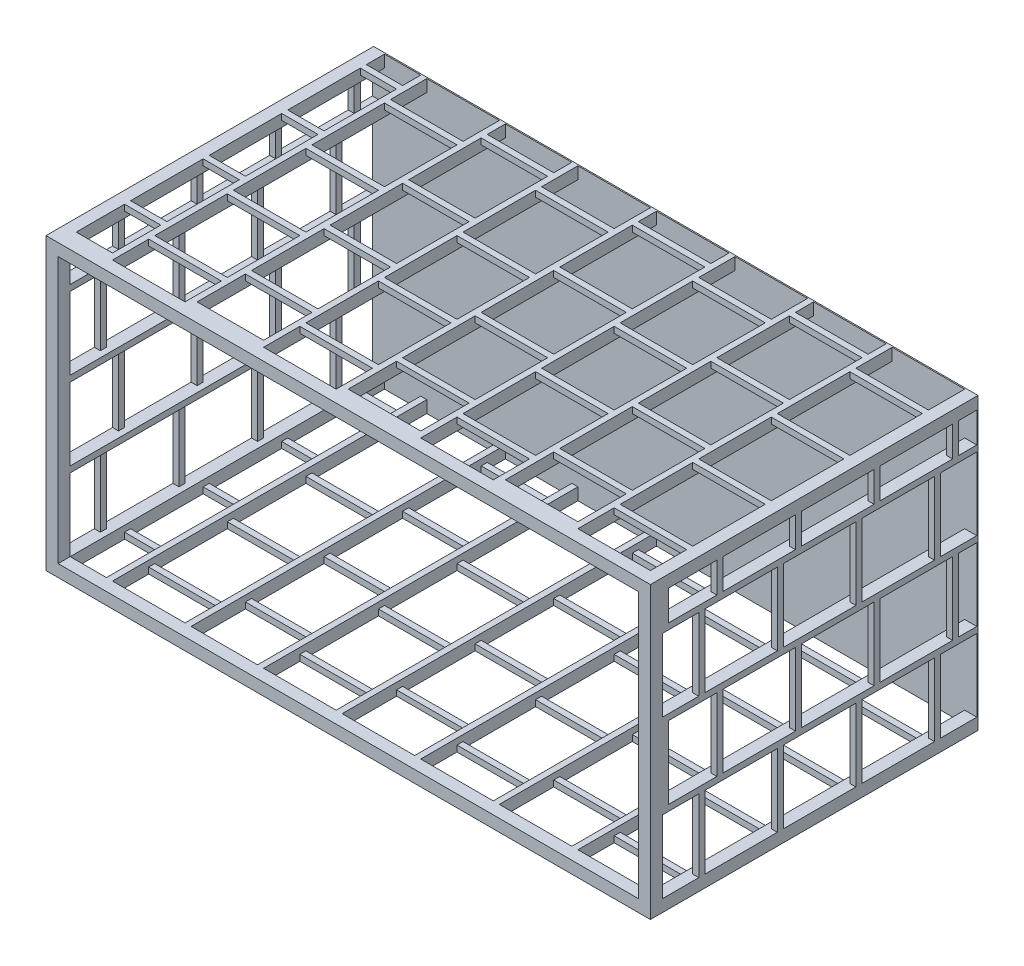
SolidWorks part; units mm, degrees
ref_plane "Plan de face" through (0, 0, 0) normal (0, 0, 1) x (1, 0, 0)
ref_plane "Plan de dessus" through (0, 0, 0) normal (0, 1, 0) x (1, 0, 0)
ref_plane "Plan de droite" through (0, 0, 0) normal (1, 0, 0) x (0, 0, -1)
sketch "Esquisse1" plane through (0, 0, 0) normal (0, 0, 1) x (1, 0, 0)
  line L1 (2500, -1200) -> (-2500, -1200)
  line L2 (2500, -1200) -> (2500, 1200)
  line L3 (2500, 1200) -> (-2500, 1200)
  line L4 (-2500, -1200) -> (-2500, 1200)
  line L5 (2500, -1200) -> (-2500, 1200) construction
  line L6 (2500, 1200) -> (-2500, -1200) construction
  point P0 (0, 0)
extrude "Boss.-Extru.1" add sketch "Esquisse1" along normal blind 10
sketch "Esquisse2" plane through (0, 0, 10) normal (0, 0, 1) x (1, 0, 0)
  line L0 (-2400, -1200) -> (-2400, -1100) construction
  line L1 (-2500, -1200) -> (2500, -1200) construction
  line L2 (-2400, -1100) -> (-2500, -1100) construction
  line L3 (-2500, 1200) -> (-2500, -1200) construction
  line L4 (0, 1200) -> (0, -1200) construction
  line L5 (-2500, -1200) -> (-2400, -1200)
  line L6 (-2500, -1200) -> (-2500, -1100)
  line L7 (-2500, -1100) -> (-2400, -1100)
  line L8 (-2400, -1200) -> (-2400, -1100)
  line L9 (2500, 1200) -> (-2500, 1200) construction
  line L10 (-2500, 0) -> (2500, 0) construction
  line L11 (2500, -1200) -> (2500, 1200) construction
  line L12 (2400, -1100) -> (2500, -1100) construction
  line L13 (2400, -1200) -> (2400, -1100) construction
  line L14 (2400, -1200) -> (2400, -1100)
  line L15 (2500, -1100) -> (2400, -1100)
  line L16 (2500, -1200) -> (2500, -1100)
  line L17 (2500, -1200) -> (2400, -1200)
  line L18 (2400, 1200) -> (2400, 1100) construction
  line L19 (2400, 1100) -> (2500, 1100) construction
  line L20 (2500, 1200) -> (2400, 1200)
  line L21 (2500, 1200) -> (2500, 1100)
  line L22 (2500, 1100) -> (2400, 1100)
  line L23 (2400, 1200) -> (2400, 1100)
  line L24 (-2400, 1100) -> (-2500, 1100) construction
  line L25 (-2400, 1200) -> (-2400, 1100) construction
  line L26 (-2400, 1200) -> (-2400, 1100)
  line L27 (-2500, 1100) -> (-2400, 1100)
  line L28 (-2500, 1200) -> (-2500, 1100)
  line L29 (-2500, 1200) -> (-2400, 1200)
extrude "Boss.-Extru.3" add sketch "Esquisse2" along normal blind 2700
sketch "Esquisse3" plane through (2400, 0, 0) normal (-1, 0, 0) x (0, 0, 1)
  line L0 (2710, 1100) -> (2610, 1100) construction
  line L1 (2710, 1100) -> (10, 1100) construction
  line L2 (2610, 1100) -> (2610, 1200) construction
  line L3 (2710, 1200) -> (10, 1200) construction
  line L4 (2610, 1200) -> (2710, 1200) construction
  line L5 (2710, 1200) -> (2710, 1100) construction
  line L7 (2710, 1100) -> (2610, 1100)
  line L8 (2710, 1100) -> (2710, 1200)
  line L9 (2710, 1200) -> (2610, 1200)
  line L10 (2610, 1100) -> (2610, 1200)
extrude "Boss.-Extru.4" add sketch "Esquisse3" along normal up to next
sketch "Esquisse4" plane through (0, 1100, 0) normal (0, -1, 0) x (1, 0, 0)
  line L1 (-2500, 2710) -> (-2400, 2710)
  line L2 (-2500, 2710) -> (-2500, 2610)
  line L3 (-2500, 2610) -> (-2400, 2610)
  line L4 (-2400, 2710) -> (-2400, 2610)
  line L5 (2400, 2610) -> (2500, 2610)
  line L6 (2400, 2610) -> (2400, 2710)
  line L7 (2400, 2710) -> (2500, 2710)
  line L8 (2500, 2610) -> (2500, 2710)
extrude "Boss.-Extru.6" add sketch "Esquisse4" along normal up to next
sketch "Esquisse5" plane through (-2400, 0, 0) normal (1, 0, 0) x (0, 0, -1)
  line L1 (-2710, -1200) -> (-2610, -1200)
  line L2 (-2710, -1200) -> (-2710, -1100)
  line L3 (-2710, -1100) -> (-2610, -1100)
  line L4 (-2610, -1200) -> (-2610, -1100)
extrude "Boss.-Extru.7" add sketch "Esquisse5" along normal up to next
sketch "Esquisse6" plane through (0, 0, 10) normal (0, 0, 1) x (1, 0, 0)
  line L0 (2400, 1200) -> (1800, 1200) construction
  line L1 (2400, 1200) -> (-2400, 1200) construction
  line L2 (2500, 0) -> (-2500, 0) construction
  line L3 (1800, 1200) -> (1750, 1200)
  line L4 (1800, 1200) -> (1800, 1100)
  line L5 (1800, 1100) -> (1750, 1100)
  line L6 (1750, 1200) -> (1750, 1100)
  line L7 (1100, 1200) -> (1150, 1200)
  line L8 (1100, 1200) -> (1100, 1100)
  line L9 (1100, 1100) -> (1150, 1100)
  line L10 (1150, 1200) -> (1150, 1100)
  line L11 (450, 1200) -> (500, 1200)
  line L12 (450, 1200) -> (450, 1100)
  line L13 (450, 1100) -> (500, 1100)
  line L14 (500, 1200) -> (500, 1100)
  line L15 (-200, 1100) -> (-150, 1100)
  line L16 (-200, 1100) -> (-200, 1200)
  line L17 (-200, 1200) -> (-150, 1200)
  line L18 (-150, 1100) -> (-150, 1200)
  line L19 (-850, 1100) -> (-800, 1100)
  line L20 (-850, 1100) -> (-850, 1200)
  line L21 (-850, 1200) -> (-800, 1200)
  line L22 (-800, 1100) -> (-800, 1200)
  line L23 (-1450, 1100) -> (-1400, 1100)
  line L24 (-1450, 1100) -> (-1450, 1200)
  line L25 (-1450, 1200) -> (-1400, 1200)
  line L26 (-1400, 1100) -> (-1400, 1200)
  line L27 (-2100, 1100) -> (-2050, 1100)
  line L28 (-2100, 1100) -> (-2100, 1200)
  line L29 (-2100, 1200) -> (-2050, 1200)
  line L30 (-2050, 1100) -> (-2050, 1200)
  line L31 (2500, -1100) -> (2500, 1100) construction
  line L32 (-2500, 1100) -> (-2500, -1100) construction
  line L33 (2400, -1200) -> (1800, -1200) construction
  line L34 (-2050, -1100) -> (-2050, -1200)
  line L35 (-2100, -1200) -> (-2050, -1200)
  line L36 (-2100, -1100) -> (-2100, -1200)
  line L37 (-2100, -1100) -> (-2050, -1100)
  line L38 (-1400, -1100) -> (-1400, -1200)
  line L39 (-1450, -1200) -> (-1400, -1200)
  line L40 (-1450, -1100) -> (-1450, -1200)
  line L41 (-1450, -1100) -> (-1400, -1100)
  line L42 (-800, -1100) -> (-800, -1200)
  line L43 (-850, -1200) -> (-800, -1200)
  line L44 (-850, -1100) -> (-850, -1200)
  line L45 (-850, -1100) -> (-800, -1100)
  line L46 (-150, -1100) -> (-150, -1200)
  line L47 (-200, -1200) -> (-150, -1200)
  line L48 (-200, -1100) -> (-200, -1200)
  line L49 (-200, -1100) -> (-150, -1100)
  line L50 (500, -1200) -> (500, -1100)
  line L51 (450, -1100) -> (500, -1100)
  line L52 (450, -1200) -> (450, -1100)
  line L53 (450, -1200) -> (500, -1200)
  line L54 (1150, -1200) -> (1150, -1100)
  line L55 (1100, -1100) -> (1150, -1100)
  line L56 (1100, -1200) -> (1100, -1100)
  line L57 (1100, -1200) -> (1150, -1200)
  line L58 (1750, -1200) -> (1750, -1100)
  line L59 (1800, -1100) -> (1750, -1100)
  line L60 (1800, -1200) -> (1800, -1100)
  line L61 (1800, -1200) -> (1750, -1200)
  point P16 (450, 1150)
  dimension "D1" = 600
  dimension "D2" = 50
  dimension "D3" = 600
  dimension "D4" = 50
  dimension "D5" = 100
  dimension "D6" = 600
  dimension "D7" = 50
  dimension "D8" = 100
  dimension "D9" = 600
  dimension "D10" = 50
  dimension "D11" = 100
  dimension "D12" = 600
  dimension "D13" = 50
  dimension "D14" = 100
  dimension "D15" = 600
  dimension "D16" = 50
  dimension "D17" = 100
  dimension "D18" = 600
  dimension "D19" = 50
  dimension "D20" = 100
  dimension "D21" = 100
extrude "Boss.-Extru.8" add sketch "Esquisse6" along normal up to next
sketch "Esquisse7" plane through (0, 0, 10) normal (0, 0, 1) x (1, 0, 0)
  line L0 (2500, -1100) -> (2500, 1100) construction
  line L1 (2500, -500) -> (2400, -500)
  line L2 (2500, -500) -> (2500, -450)
  line L3 (2500, -450) -> (2400, -450)
  line L4 (2400, -500) -> (2400, -450)
  line L5 (0, -1200) -> (0, 1200) construction
  line L6 (2500, 150) -> (2400, 150)
  line L7 (2500, 150) -> (2500, 200)
  line L8 (2500, 200) -> (2400, 200)
  line L9 (2400, 150) -> (2400, 200)
  line L10 (2500, 800) -> (2400, 800)
  line L11 (2500, 800) -> (2500, 850)
  line L12 (2500, 850) -> (2400, 850)
  line L13 (2400, 800) -> (2400, 850)
  line L14 (-150, -1200) -> (450, -1200) construction
  line L15 (450, 1200) -> (-150, 1200) construction
  line L16 (-2500, 850) -> (-2400, 850)
  line L17 (-2500, 800) -> (-2500, 850)
  line L18 (-2500, 800) -> (-2400, 800)
  line L19 (-2400, -500) -> (-2400, -450)
  line L20 (-2500, -450) -> (-2400, -450)
  line L21 (-2500, -500) -> (-2500, -450)
  line L22 (-2500, -500) -> (-2400, -500)
  line L23 (-2400, 800) -> (-2400, 850)
  line L24 (-2400, 150) -> (-2400, 200)
  line L25 (-2500, 200) -> (-2400, 200)
  line L26 (-2500, 150) -> (-2500, 200)
  line L27 (-2500, 150) -> (-2400, 150)
  dimension "D1" = 600
  dimension "D2" = 100
  dimension "D3" = 50
  dimension "D4" = 600
  dimension "D5" = 100
  dimension "D6" = 50
  dimension "D7" = 600
  dimension "D8" = 100
  dimension "D9" = 50
extrude "Boss.-Extru.9" add sketch "Esquisse7" along normal up to next
sketch "Esquisse8" plane through (2400, 0, 0) normal (-1, 0, 0) x (0, 0, 1)
  line L0 (2610, 1200) -> (10, 1200) construction
  line L1 (310, 1200) -> (360, 1200)
  line L2 (310, 1200) -> (310, 1150)
  line L3 (310, 1150) -> (360, 1150)
  line L4 (360, 1200) -> (360, 1150)
  line L5 (0, 0) -> (2710, 0) construction
  line L6 (960, 1200) -> (1010, 1200)
  line L7 (960, 1200) -> (960, 1150)
  line L8 (960, 1150) -> (1010, 1150)
  line L9 (1010, 1200) -> (1010, 1150)
  line L10 (1610, 1200) -> (1660, 1200)
  line L11 (1610, 1200) -> (1610, 1150)
  line L12 (1610, 1150) -> (1660, 1150)
  line L13 (1660, 1200) -> (1660, 1150)
  line L14 (2260, 1200) -> (2310, 1200)
  line L15 (2260, 1200) -> (2260, 1150)
  line L16 (2260, 1150) -> (2310, 1150)
  line L17 (2310, 1200) -> (2310, 1150)
  line L18 (2710, 1200) -> (2710, -1200) construction
  line L19 (2310, -1200) -> (2310, -1150)
  line L20 (2260, -1150) -> (2310, -1150)
  line L21 (2260, -1200) -> (2260, -1150)
  line L22 (2260, -1200) -> (2310, -1200)
  line L23 (1660, -1200) -> (1660, -1150)
  line L24 (1610, -1150) -> (1660, -1150)
  line L25 (1610, -1200) -> (1610, -1150)
  line L26 (1610, -1200) -> (1660, -1200)
  line L27 (1010, -1200) -> (1010, -1150)
  line L28 (960, -1150) -> (1010, -1150)
  line L29 (960, -1200) -> (960, -1150)
  line L30 (960, -1200) -> (1010, -1200)
  line L31 (360, -1200) -> (360, -1150)
  line L32 (310, -1150) -> (360, -1150)
  line L33 (310, -1200) -> (310, -1150)
  line L34 (310, -1200) -> (360, -1200)
  dimension "D1" = 300
  dimension "D2" = 50
  dimension "D3" = 50
  dimension "D4" = 600
  dimension "D5" = 50
  dimension "D6" = 50
  dimension "D7" = 600
  dimension "D8" = 50
  dimension "D9" = 50
  dimension "D10" = 600
  dimension "D12" = 50
extrude "Boss.-Extru.11" add sketch "Esquisse8" along normal up to next
sketch "Esquisse9" plane through (1750, 0, 0) normal (-1, 0, 0) x (0, 0, 1)
  line L0 (2610, 1200) -> (10, 1200) construction
  line L1 (10, 1200) -> (10, 1100) construction
  line L2 (160, 1200) -> (210, 1200)
  line L3 (160, 1200) -> (160, 1150)
  line L4 (160, 1150) -> (210, 1150)
  line L6 (210, 1200) -> (210, 1150)
  line L7 (860, 1200) -> (810, 1200)
  line L8 (860, 1200) -> (860, 1150)
  line L9 (860, 1150) -> (810, 1150)
  line L10 (0, 0) -> (2710, 0) construction
  line L11 (810, 1200) -> (810, 1150)
  line L12 (1510, 1200) -> (1460, 1200)
  line L13 (1510, 1200) -> (1510, 1150)
  line L14 (1510, 1150) -> (1460, 1150)
  line L15 (1460, 1200) -> (1460, 1150)
  line L16 (2110, 1200) -> (2160, 1200)
  line L17 (2110, 1200) -> (2110, 1150)
  line L18 (2110, 1150) -> (2160, 1150)
  line L19 (2160, 1200) -> (2160, 1150)
  line L20 (2610, 1200) -> (2560, 1200)
  line L21 (2610, 1200) -> (2610, 1150)
  line L22 (2610, 1150) -> (2560, 1150)
  line L23 (2710, 1200) -> (2710, -1200) construction
  line L24 (2560, -1200) -> (2560, -1150)
  line L25 (2610, -1150) -> (2560, -1150)
  line L26 (2610, -1200) -> (2610, -1150)
  line L27 (2610, -1200) -> (2560, -1200)
  line L28 (2160, -1200) -> (2160, -1150)
  line L29 (2110, -1150) -> (2160, -1150)
  line L30 (2110, -1200) -> (2110, -1150)
  line L31 (2110, -1200) -> (2160, -1200)
  line L32 (1460, -1200) -> (1460, -1150)
  line L33 (1510, -1150) -> (1460, -1150)
  line L34 (1510, -1200) -> (1510, -1150)
  line L35 (1510, -1200) -> (1460, -1200)
  line L36 (810, -1200) -> (810, -1150)
  line L37 (860, -1150) -> (810, -1150)
  line L38 (860, -1200) -> (860, -1150)
  line L39 (860, -1200) -> (810, -1200)
  line L40 (210, -1200) -> (210, -1150)
  line L41 (160, -1150) -> (210, -1150)
  line L42 (160, -1200) -> (160, -1150)
  line L43 (160, -1200) -> (210, -1200)
  line L44 (2560, 1200) -> (2560, 1150)
  dimension "D2" = 150
  dimension "D3" = 50
  dimension "D4" = 50
  dimension "D5" = 50
  dimension "D6" = 50
  dimension "D7" = 50
  dimension "D8" = 50
  dimension "D9" = 50
  dimension "D10" = 50
  dimension "D11" = 50
  dimension "D12" = 400
  dimension "D13" = 600
  dimension "D14" = 600
  dimension "D15" = 50
  dimension "D16" = 600
extrude "Boss.-Extru.12" add sketch "Esquisse9" along normal up to next
sketch "Esquisse10" plane through (1100, 0, 0) normal (-1, 0, 0) x (0, 0, 1)
  line L0 (2610, 1200) -> (10, 1200) construction
  line L1 (2260, -1200) -> (2260, -1150)
  line L2 (310, 1200) -> (360, 1200)
  line L3 (310, 1200) -> (310, 1150)
  line L4 (310, 1150) -> (360, 1150)
  line L7 (0, 0) -> (2710, 0) construction
  line L8 (360, 1200) -> (360, 1150)
  line L9 (960, 1200) -> (1010, 1200)
  line L10 (960, 1200) -> (960, 1150)
  line L11 (960, 1150) -> (1010, 1150)
  line L12 (1010, 1200) -> (1010, 1150)
  line L13 (1660, 1200) -> (1610, 1200)
  line L14 (1660, 1200) -> (1660, 1150)
  line L15 (1660, 1150) -> (1610, 1150)
  line L16 (1610, 1200) -> (1610, 1150)
  line L17 (2310, 1200) -> (2260, 1200)
  line L18 (2310, 1200) -> (2310, 1150)
  line L19 (2310, 1150) -> (2260, 1150)
  line L20 (2710, 1200) -> (2710, -1200) construction
  line L21 (2310, -1150) -> (2260, -1150)
  line L22 (2310, -1200) -> (2310, -1150)
  line L23 (2310, -1200) -> (2260, -1200)
  line L24 (1610, -1200) -> (1610, -1150)
  line L25 (1660, -1150) -> (1610, -1150)
  line L26 (1660, -1200) -> (1660, -1150)
  line L27 (1660, -1200) -> (1610, -1200)
  line L28 (1010, -1200) -> (1010, -1150)
  line L29 (960, -1150) -> (1010, -1150)
  line L30 (960, -1200) -> (960, -1150)
  line L31 (960, -1200) -> (1010, -1200)
  line L32 (360, -1200) -> (360, -1150)
  line L33 (310, -1150) -> (360, -1150)
  line L34 (310, -1200) -> (310, -1150)
  line L35 (310, -1200) -> (360, -1200)
  line L37 (2260, 1200) -> (2260, 1150)
  point P43 (1610, 1175)
  dimension "D2" = 50
  dimension "D3" = 50
  dimension "D4" = 50
  dimension "D5" = 50
  dimension "D6" = 50
  dimension "D7" = 50
  dimension "D8" = 50
  dimension "D9" = 600
  dimension "D10" = 600
  dimension "D11" = 50
  dimension "D12" = 600
extrude "Boss.-Extru.13" add sketch "Esquisse10" along normal up to next
sketch "Esquisse11" plane through (450, 0, 0) normal (-1, 0, 0) x (0, 0, 1)
  line L0 (2610, 1200) -> (10, 1200) construction
  line L1 (2610, 1200) -> (2610, 1100) construction
  line L2 (2560, 1200) -> (2610, 1200)
  line L3 (2560, 1200) -> (2560, 1150)
  line L4 (2560, 1150) -> (2610, 1150)
  line L6 (2110, -1200) -> (2110, -1154.4562)
  line L7 (0, 0) -> (2710, 0) construction
  line L8 (2610, -1200) -> (2610, -1150)
  line L9 (2160, 1200) -> (2110, 1200)
  line L10 (2160, 1200) -> (2160, 1154.4562)
  line L11 (2160, 1154.4562) -> (2110, 1154.4562)
  line L12 (1510, 1200) -> (1460, 1200)
  line L13 (1510, 1200) -> (1510, 1150)
  line L14 (1510, 1150) -> (1460, 1150)
  line L15 (1460, 1200) -> (1460, 1150)
  line L16 (160, 1200) -> (210, 1200)
  line L17 (160, 1200) -> (160, 1150)
  line L18 (160, 1150) -> (210, 1150)
  line L19 (210, 1200) -> (210, 1150)
  line L20 (860, 1200) -> (810, 1200)
  line L21 (860, 1200) -> (860, 1150)
  line L22 (860, 1150) -> (810, 1150)
  line L23 (810, 1200) -> (810, 1150)
  line L24 (2710, 1200) -> (2710, -1200) construction
  line L25 (810, -1200) -> (810, -1150)
  line L26 (860, -1150) -> (810, -1150)
  line L27 (860, -1200) -> (860, -1150)
  line L28 (860, -1200) -> (810, -1200)
  line L29 (210, -1200) -> (210, -1150)
  line L30 (160, -1150) -> (210, -1150)
  line L31 (160, -1200) -> (160, -1150)
  line L32 (160, -1200) -> (210, -1200)
  line L33 (1460, -1200) -> (1460, -1150)
  line L34 (1510, -1150) -> (1460, -1150)
  line L35 (1510, -1200) -> (1510, -1150)
  line L36 (1510, -1200) -> (1460, -1200)
  line L37 (2160, -1154.4562) -> (2110, -1154.4562)
  line L38 (2160, -1200) -> (2160, -1154.4562)
  line L39 (2160, -1200) -> (2110, -1200)
  line L40 (2560, -1150) -> (2610, -1150)
  line L41 (2560, -1200) -> (2560, -1150)
  line L42 (2560, -1200) -> (2610, -1200)
  line L45 (2610, 1200) -> (2610, 1150)
  line L46 (2110, 1200) -> (2110, 1154.4562)
  dimension "D2" = 50
  dimension "D3" = 50
  dimension "D4" = 400
  dimension "D5" = 50
  dimension "D6" = 50
  dimension "D7" = 50
  dimension "D8" = 50
  dimension "D9" = 50
  dimension "D10" = 50
  dimension "D11" = 600
  dimension "D12" = 600
  dimension "D13" = 600
extrude "Boss.-Extru.14" add sketch "Esquisse11" along normal up to next
sketch "Esquisse12" plane through (-200, 0, 0) normal (-1, 0, 0) x (0, 0, 1)
  line L0 (2610, 1200) -> (10, 1200) construction
  line L1 (10, 1200) -> (10, 1100) construction
  line L2 (360, 1200) -> (310, 1200)
  line L3 (360, 1200) -> (360, 1150)
  line L4 (360, 1150) -> (310, 1150)
  line L7 (2610, 1200) -> (2610, 1100) construction
  line L8 (0, 0) -> (2710, 0) construction
  line L10 (960, 1200) -> (1010, 1200)
  line L11 (960, 1200) -> (960, 1150)
  line L12 (960, 1150) -> (1010, 1150)
  line L13 (1010, 1200) -> (1010, 1150)
  line L14 (1610, 1200) -> (1660, 1200)
  line L15 (1610, 1200) -> (1610, 1150)
  line L16 (1610, 1150) -> (1660, 1150)
  line L17 (310, 1200) -> (310, 1150)
  line L18 (2310, 1200) -> (2260, 1200)
  line L19 (2310, 1200) -> (2310, 1150)
  line L20 (2310, 1150) -> (2260, 1150)
  line L21 (2710, 1200) -> (2710, -1200) construction
  line L22 (1660, -1200) -> (1660, -1150)
  line L23 (2260, -1200) -> (2260, -1150)
  line L24 (2310, -1150) -> (2260, -1150)
  line L25 (2310, -1200) -> (2310, -1150)
  line L26 (2310, -1200) -> (2260, -1200)
  line L27 (310, -1200) -> (310, -1150)
  line L28 (1610, -1150) -> (1660, -1150)
  line L29 (1610, -1200) -> (1610, -1150)
  line L30 (1610, -1200) -> (1660, -1200)
  line L31 (1010, -1200) -> (1010, -1150)
  line L32 (960, -1150) -> (1010, -1150)
  line L33 (960, -1200) -> (960, -1150)
  line L34 (960, -1200) -> (1010, -1200)
  line L35 (360, -1150) -> (310, -1150)
  line L36 (360, -1200) -> (360, -1150)
  line L37 (360, -1200) -> (310, -1200)
  line L38 (2260, 1200) -> (2260, 1150)
  line L39 (1660, 1200) -> (1660, 1150)
  dimension "D2" = 50
  dimension "D3" = 50
  dimension "D4" = 50
  dimension "D5" = 50
  dimension "D6" = 50
  dimension "D7" = 50
  dimension "D8" = 50
  dimension "D9" = 600
  dimension "D10" = 600
  dimension "D11" = 300
  dimension "D12" = 50
  dimension "D13" = 600
  dimension "D14" = 300
extrude "Boss.-Extru.15" add sketch "Esquisse12" along normal up to next
sketch "Esquisse13" plane through (-850, 0, 0) normal (-1, 0, 0) x (0, 0, 1)
  line L0 (2610, 1200) -> (10, 1200) construction
  line L1 (10, 1200) -> (10, 1100) construction
  line L2 (160, 1200) -> (210, 1200)
  line L3 (160, 1200) -> (160, 1150)
  line L4 (160, 1150) -> (210, 1150)
  line L7 (0, 0) -> (2710, 0) construction
  line L9 (810, 1200) -> (860, 1200)
  line L10 (810, 1200) -> (810, 1150)
  line L11 (810, 1150) -> (860, 1150)
  line L12 (860, 1200) -> (860, 1150)
  line L13 (1460, 1200) -> (1510, 1200)
  line L14 (1460, 1200) -> (1460, 1150)
  line L15 (1460, 1150) -> (1510, 1150)
  line L16 (1510, 1200) -> (1510, 1150)
  line L17 (2160, 1200) -> (2110, 1200)
  line L18 (2160, 1200) -> (2160, 1150)
  line L19 (2160, 1150) -> (2110, 1150)
  line L20 (2110, 1200) -> (2110, 1150)
  line L21 (2610, 1200) -> (2560, 1200)
  line L22 (2610, 1200) -> (2610, 1150)
  line L23 (2610, 1150) -> (2560, 1150)
  line L24 (2710, 1200) -> (2710, -1200) construction
  line L25 (210, -1200) -> (210, -1150)
  line L26 (2560, -1200) -> (2560, -1150)
  line L27 (2610, -1150) -> (2560, -1150)
  line L28 (2610, -1200) -> (2610, -1150)
  line L29 (2610, -1200) -> (2560, -1200)
  line L30 (2110, -1200) -> (2110, -1150)
  line L31 (2160, -1150) -> (2110, -1150)
  line L32 (2160, -1200) -> (2160, -1150)
  line L33 (2160, -1200) -> (2110, -1200)
  line L34 (1510, -1200) -> (1510, -1150)
  line L35 (1460, -1150) -> (1510, -1150)
  line L36 (1460, -1200) -> (1460, -1150)
  line L37 (1460, -1200) -> (1510, -1200)
  line L38 (860, -1200) -> (860, -1150)
  line L39 (810, -1150) -> (860, -1150)
  line L40 (810, -1200) -> (810, -1150)
  line L41 (810, -1200) -> (860, -1200)
  line L42 (160, -1150) -> (210, -1150)
  line L43 (160, -1200) -> (160, -1150)
  line L44 (160, -1200) -> (210, -1200)
  line L45 (2560, 1200) -> (2560, 1150)
  line L46 (210, 1200) -> (210, 1150)
  dimension "D2" = 50
  dimension "D3" = 50
  dimension "D4" = 50
  dimension "D5" = 50
  dimension "D6" = 50
  dimension "D7" = 50
  dimension "D8" = 50
  dimension "D9" = 50
  dimension "D10" = 50
  dimension "D11" = 400
  dimension "D12" = 600
  dimension "D13" = 600
  dimension "D14" = 50
  dimension "D15" = 600
  dimension "D16" = 150
extrude "Boss.-Extru.16" add sketch "Esquisse13" along normal up to next
sketch "Esquisse14" plane through (-1450, 0, 0) normal (-1, 0, 0) x (0, 0, 1)
  line L1 (10, 1200) -> (10, 1100) construction
  line L2 (360, 1200) -> (310, 1200)
  line L3 (360, 1200) -> (360, 1150)
  line L4 (360, 1150) -> (310, 1150)
  line L5 (2610, 1200) -> (10, 1200) construction
  line L7 (0, 0) -> (2710, 0) construction
  line L8 (310, 1200) -> (310, 1150)
  line L9 (960, 1200) -> (1010, 1200)
  line L10 (960, 1200) -> (960, 1150)
  line L11 (960, 1150) -> (1010, 1150)
  line L12 (1010, 1200) -> (1010, 1150)
  line L13 (1610, 1200) -> (1660, 1200)
  line L14 (1610, 1200) -> (1610, 1150)
  line L15 (1610, 1150) -> (1660, 1150)
  line L16 (2610, 1200) -> (2610, 1100) construction
  line L17 (2310, 1200) -> (2260, 1200)
  line L18 (2310, 1200) -> (2310, 1150)
  line L19 (2310, 1150) -> (2260, 1150)
  line L20 (2710, 1200) -> (2710, -1200) construction
  line L21 (1660, -1200) -> (1660, -1150)
  line L22 (2260, -1200) -> (2260, -1150)
  line L23 (2310, -1150) -> (2260, -1150)
  line L24 (2310, -1200) -> (2310, -1150)
  line L25 (2310, -1200) -> (2260, -1200)
  line L26 (1610, -1150) -> (1660, -1150)
  line L27 (1610, -1200) -> (1610, -1150)
  line L28 (1610, -1200) -> (1660, -1200)
  line L29 (1010, -1200) -> (1010, -1150)
  line L30 (960, -1150) -> (1010, -1150)
  line L31 (960, -1200) -> (960, -1150)
  line L32 (960, -1200) -> (1010, -1200)
  line L33 (310, -1200) -> (310, -1150)
  line L34 (360, -1150) -> (310, -1150)
  line L35 (360, -1200) -> (360, -1150)
  line L36 (360, -1200) -> (310, -1200)
  line L37 (2260, 1200) -> (2260, 1150)
  line L38 (1660, 1200) -> (1660, 1150)
  point P45 (2610, 1150)
  dimension "D2" = 50
  dimension "D3" = 50
  dimension "D4" = 50
  dimension "D5" = 50
  dimension "D6" = 50
  dimension "D7" = 50
  dimension "D8" = 50
  dimension "D9" = 300
  dimension "D10" = 600
  dimension "D11" = 600
  dimension "D12" = 50
  dimension "D13" = 600
  dimension "D14" = 300
extrude "Boss.-Extru.17" add sketch "Esquisse14" along normal up to next
sketch "Esquisse15" plane through (-2100, 0, 0) normal (-1, 0, 0) x (0, 0, 1)
  line L2 (160, 1200) -> (210, 1200)
  line L3 (160, 1200) -> (160, 1150)
  line L4 (160, 1150) -> (210, 1150)
  line L5 (1510, -1200) -> (1510, -1150)
  line L6 (2560, -1200) -> (2560, -1150)
  line L7 (0, 0) -> (2710, 0) construction
  line L8 (210, 1200) -> (210, 1150)
  line L9 (810, 1200) -> (860, 1200)
  line L10 (810, 1200) -> (810, 1150)
  line L11 (810, 1150) -> (860, 1150)
  line L12 (2610, -1150) -> (2560, -1150)
  line L13 (860, 1200) -> (860, 1150)
  line L14 (1460, 1200) -> (1510, 1200)
  line L15 (1460, 1200) -> (1460, 1150)
  line L16 (1460, 1150) -> (1510, 1150)
  line L17 (2110, 1200) -> (2160, 1200)
  line L18 (2110, 1200) -> (2110, 1150)
  line L19 (2110, 1150) -> (2160, 1150)
  line L20 (2160, 1200) -> (2160, 1150)
  line L21 (2610, 1200) -> (2560, 1200)
  line L22 (2610, 1200) -> (2610, 1150)
  line L23 (2610, 1150) -> (2560, 1150)
  line L24 (2710, 1200) -> (2710, -1200) construction
  line L25 (2610, -1200) -> (2610, -1150)
  line L26 (2610, -1200) -> (2560, -1200)
  line L27 (2160, -1200) -> (2160, -1150)
  line L28 (2110, -1150) -> (2160, -1150)
  line L29 (2110, -1200) -> (2110, -1150)
  line L30 (2110, -1200) -> (2160, -1200)
  line L31 (1460, -1150) -> (1510, -1150)
  line L32 (1460, -1200) -> (1460, -1150)
  line L33 (1460, -1200) -> (1510, -1200)
  line L34 (860, -1200) -> (860, -1150)
  line L35 (810, -1150) -> (860, -1150)
  line L36 (810, -1200) -> (810, -1150)
  line L37 (810, -1200) -> (860, -1200)
  line L38 (210, -1200) -> (210, -1150)
  line L39 (160, -1150) -> (210, -1150)
  line L40 (160, -1200) -> (160, -1150)
  line L41 (160, -1200) -> (210, -1200)
  line L42 (2560, 1200) -> (2560, 1150)
  line L43 (1510, 1200) -> (1510, 1150)
extrude "Boss.-Extru.18" add sketch "Esquisse15" along normal up to next
sketch "Esquisse16" plane through (0, -1100, 0) normal (0, 1, 0) x (1, 0, 0)
  line L1 (2500, -2610) -> (2500, -10) construction
  line L2 (2500, -310) -> (2450, -310)
  line L3 (2500, -310) -> (2500, -360)
  line L4 (2500, -360) -> (2450, -360)
  line L6 (2450, -310) -> (2450, -360)
  line L7 (2500, -10) -> (2400, -10) construction
  line L8 (0, 0) -> (0, -2710) construction
  line L9 (2500, -960) -> (2450, -960)
  line L10 (2500, -960) -> (2500, -1010)
  line L11 (2500, -1010) -> (2450, -1010)
  line L12 (2450, -960) -> (2450, -1010)
  line L13 (2500, -1610) -> (2450, -1610)
  line L14 (2500, -1610) -> (2500, -1660)
  line L15 (2500, -1660) -> (2450, -1660)
  line L16 (2450, -1610) -> (2450, -1660)
  line L17 (2500, -2260) -> (2450, -2260)
  line L18 (2500, -2260) -> (2500, -2310)
  line L19 (2500, -2310) -> (2450, -2310)
  line L20 (2450, -2260) -> (2450, -2310)
  line L21 (2500, -2710) -> (-2500, -2710) construction
  line L22 (-2450, -2260) -> (-2450, -2310)
  line L23 (-2500, -2310) -> (-2450, -2310)
  line L24 (-2500, -2260) -> (-2500, -2310)
  line L25 (-2500, -2260) -> (-2450, -2260)
  line L26 (-2450, -1610) -> (-2450, -1660)
  line L27 (-2500, -1660) -> (-2450, -1660)
  line L28 (-2500, -1610) -> (-2500, -1660)
  line L29 (-2500, -1610) -> (-2450, -1610)
  line L30 (-2450, -960) -> (-2450, -1010)
  line L31 (-2500, -1010) -> (-2450, -1010)
  line L32 (-2500, -960) -> (-2500, -1010)
  line L33 (-2500, -960) -> (-2450, -960)
  line L34 (-2450, -310) -> (-2450, -360)
  line L35 (-2500, -360) -> (-2450, -360)
  line L36 (-2500, -310) -> (-2500, -360)
  line L37 (-2500, -310) -> (-2450, -310)
  dimension "D1" = 50
  dimension "D2" = 50
  dimension "D3" = 300
  dimension "D4" = 50
  dimension "D5" = 50
  dimension "D6" = 600
  dimension "D7" = 50
  dimension "D8" = 50
  dimension "D9" = 600
  dimension "D10" = 50
  dimension "D11" = 50
  dimension "D12" = 600
extrude "Boss.-Extru.19" add sketch "Esquisse16" along normal up to next
sketch "Esquisse17" plane through (0, -450, 0) normal (0, 1, 0) x (1, 0, 0)
  line L0 (2500, -2610) -> (2500, -10) construction
  line L1 (2500, -10) -> (2400, -10) construction
  line L2 (2500, -160) -> (2450, -160)
  line L3 (2500, -160) -> (2500, -210)
  line L4 (2500, -210) -> (2450, -210)
  line L7 (0, 0) -> (0, -2710) construction
  line L8 (2450, -160) -> (2450, -210)
  line L9 (2500, -810) -> (2450, -810)
  line L10 (2500, -810) -> (2500, -860)
  line L11 (2500, -860) -> (2450, -860)
  line L12 (2450, -810) -> (2450, -860)
  line L13 (2500, -1460) -> (2450, -1460)
  line L14 (2500, -1460) -> (2500, -1510)
  line L15 (2500, -1510) -> (2450, -1510)
  line L16 (2450, -1460) -> (2450, -1510)
  line L17 (2500, -2110) -> (2450, -2110)
  line L18 (2500, -2110) -> (2500, -2160)
  line L19 (2500, -2160) -> (2450, -2160)
  line L20 (-2450, -2560) -> (-2450, -2610)
  line L21 (2500, -2560) -> (2450, -2560)
  line L22 (2500, -2560) -> (2500, -2610)
  line L23 (2500, -2610) -> (2450, -2610)
  line L24 (2500, -2710) -> (-2500, -2710) construction
  line L25 (-2450, -2110) -> (-2450, -2160)
  line L26 (-2500, -2610) -> (-2450, -2610)
  line L27 (-2500, -2560) -> (-2500, -2610)
  line L28 (-2500, -2560) -> (-2450, -2560)
  line L29 (-2500, -2160) -> (-2450, -2160)
  line L30 (-2500, -2110) -> (-2500, -2160)
  line L31 (-2500, -2110) -> (-2450, -2110)
  line L32 (-2450, -1460) -> (-2450, -1510)
  line L33 (-2500, -1510) -> (-2450, -1510)
  line L34 (-2500, -1460) -> (-2500, -1510)
  line L35 (-2500, -1460) -> (-2450, -1460)
  line L36 (-2450, -810) -> (-2450, -860)
  line L37 (-2500, -860) -> (-2450, -860)
  line L38 (-2500, -810) -> (-2500, -860)
  line L39 (-2500, -810) -> (-2450, -810)
  line L40 (-2450, -160) -> (-2450, -210)
  line L41 (-2500, -210) -> (-2450, -210)
  line L42 (-2500, -160) -> (-2500, -210)
  line L43 (-2500, -160) -> (-2450, -160)
  line L45 (2450, -2110) -> (2450, -2160)
  line L46 (2450, -2560) -> (2450, -2610)
  dimension "D2" = 50
  dimension "D3" = 50
  dimension "D4" = 50
  dimension "D5" = 50
  dimension "D6" = 50
  dimension "D7" = 50
  dimension "D8" = 50
  dimension "D9" = 50
  dimension "D10" = 600
  dimension "D11" = 600
  dimension "D12" = 50
  dimension "D13" = 600
  dimension "D14" = 150
  dimension "D15" = 50
  dimension "D16" = 400
extrude "Boss.-Extru.20" add sketch "Esquisse17" along normal up to next
sketch "Esquisse18" plane through (0, 200, 0) normal (0, 1, 0) x (1, 0, 0)
  line L0 (2500, -2610) -> (2500, -10) construction
  line L1 (2500, -10) -> (2400, -10) construction
  line L2 (2500, -310) -> (2450, -310)
  line L3 (2500, -310) -> (2500, -360)
  line L4 (2500, -360) -> (2450, -360)
  line L7 (-2450, -1010) -> (-2450, -960)
  line L8 (-2450, -310) -> (-2450, -360)
  line L9 (2500, -1010) -> (2450, -1010)
  line L10 (2500, -1010) -> (2500, -960)
  line L11 (2500, -960) -> (2450, -960)
  line L12 (2500, -1610) -> (2450, -1610)
  line L13 (2500, -1610) -> (2500, -1660)
  line L14 (2500, -1660) -> (2450, -1660)
  line L15 (2450, -1610) -> (2450, -1660)
  line L16 (2500, -2260) -> (2450, -2260)
  line L17 (2500, -2260) -> (2500, -2310)
  line L18 (2500, -2310) -> (2450, -2310)
  line L19 (2450, -2260) -> (2450, -2310)
  line L20 (-2450, -2260) -> (-2450, -2310)
  line L21 (0, 0) -> (0, -2710) construction
  line L22 (2500, -2710) -> (-2500, -2710) construction
  line L23 (-2500, -2310) -> (-2450, -2310)
  line L24 (-2500, -2260) -> (-2500, -2310)
  line L25 (-2500, -2260) -> (-2450, -2260)
  line L26 (-2450, -1610) -> (-2450, -1660)
  line L27 (-2500, -1660) -> (-2450, -1660)
  line L28 (-2500, -1610) -> (-2500, -1660)
  line L29 (-2500, -1610) -> (-2450, -1610)
  line L30 (-2500, -960) -> (-2450, -960)
  line L31 (-2500, -1010) -> (-2500, -960)
  line L32 (-2500, -1010) -> (-2450, -1010)
  line L33 (-2500, -360) -> (-2450, -360)
  line L34 (-2500, -310) -> (-2500, -360)
  line L35 (-2500, -310) -> (-2450, -310)
  line L37 (2450, -310) -> (2450, -360)
  line L38 (2450, -1010) -> (2450, -960)
  point P43 (2450, -10)
  dimension "D1" = 50
  dimension "D2" = 50
  dimension "D3" = 50
  dimension "D4" = 300
  dimension "D5" = 50
  dimension "D6" = 50
  dimension "D7" = 50
  dimension "D8" = 50
  dimension "D9" = 600
  dimension "D10" = 50
  dimension "D11" = 600
  dimension "D12" = 600
extrude "Boss.-Extru.21" add sketch "Esquisse18" along normal up to next
sketch "Esquisse19" plane through (0, 850, 0) normal (0, 1, 0) x (1, 0, 0)
  line L0 (2500, -2610) -> (2500, -10) construction
  line L2 (2500, -160) -> (2450, -160)
  line L3 (2500, -160) -> (2500, -210)
  line L4 (2500, -210) -> (2450, -210)
  line L7 (2450, -160) -> (2450, -210)
  line L8 (2500, -810) -> (2450, -810)
  line L9 (2500, -810) -> (2500, -860)
  line L10 (2500, -860) -> (2450, -860)
  line L11 (2450, -810) -> (2450, -860)
  line L12 (2500, -1460) -> (2450, -1460)
  line L13 (2500, -1460) -> (2500, -1510)
  line L14 (2500, -1510) -> (2450, -1510)
  line L15 (2450, -1460) -> (2450, -1510)
  line L16 (2500, -2110) -> (2450, -2110)
  line L17 (2500, -2110) -> (2500, -2160)
  line L18 (2500, -2160) -> (2450, -2160)
  line L19 (2450, -2110) -> (2450, -2160)
  line L20 (2500, -2560) -> (2450, -2560)
  line L21 (2500, -2560) -> (2500, -2610)
  line L22 (2500, -2610) -> (2450, -2610)
  line L23 (2450, -2560) -> (2450, -2610)
  line L24 (2500, -10) -> (2400, -10) construction
  line L25 (0, 0) -> (0, -2710) construction
  line L26 (2500, -2710) -> (-2500, -2710) construction
  line L27 (-2450, -2560) -> (-2450, -2610)
  line L28 (-2500, -2610) -> (-2450, -2610)
  line L29 (-2500, -2560) -> (-2500, -2610)
  line L30 (-2500, -2560) -> (-2450, -2560)
  line L31 (-2450, -2110) -> (-2450, -2160)
  line L32 (-2500, -2160) -> (-2450, -2160)
  line L33 (-2500, -2110) -> (-2500, -2160)
  line L34 (-2500, -2110) -> (-2450, -2110)
  line L35 (-2450, -1460) -> (-2450, -1510)
  line L36 (-2500, -1510) -> (-2450, -1510)
  line L37 (-2500, -1460) -> (-2500, -1510)
  line L38 (-2500, -1460) -> (-2450, -1460)
  line L39 (-2450, -810) -> (-2450, -860)
  line L40 (-2500, -860) -> (-2450, -860)
  line L41 (-2500, -810) -> (-2500, -860)
  line L42 (-2500, -810) -> (-2450, -810)
  line L43 (-2450, -160) -> (-2450, -210)
  line L44 (-2500, -210) -> (-2450, -210)
  line L45 (-2500, -160) -> (-2500, -210)
  line L46 (-2500, -160) -> (-2450, -160)
  dimension "D2" = 50
  dimension "D3" = 50
  dimension "D4" = 50
  dimension "D5" = 50
  dimension "D6" = 50
  dimension "D7" = 50
  dimension "D8" = 50
  dimension "D9" = 600
  dimension "D10" = 600
  dimension "D11" = 50
  dimension "D12" = 600
  dimension "D13" = 50
  dimension "D14" = 50
  dimension "D15" = 400
  dimension "D16" = 150
extrude "Boss.-Extru.22" add sketch "Esquisse19" along normal up to next
